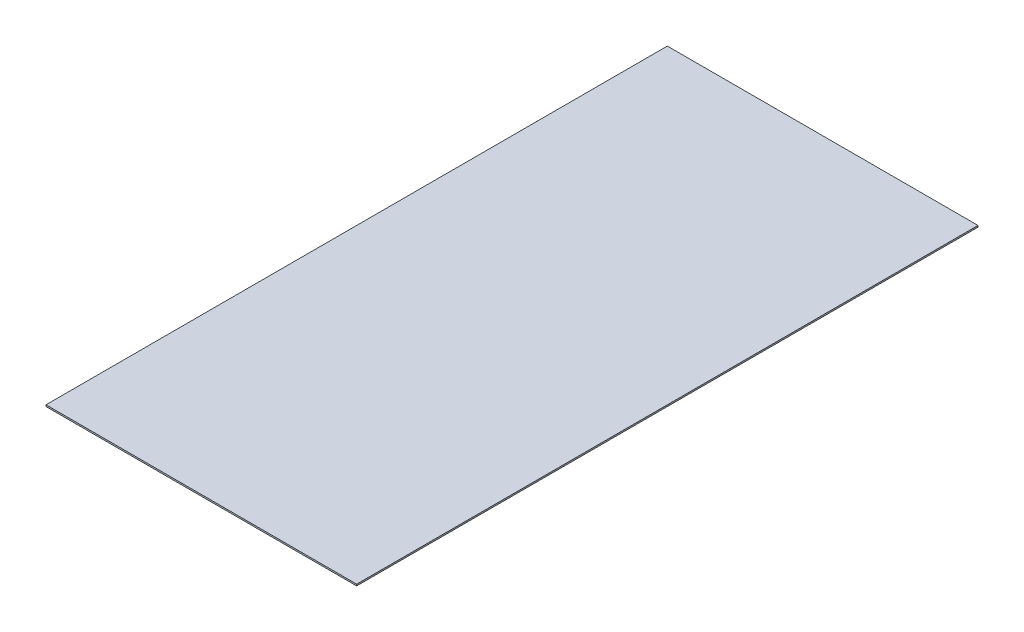
SolidWorks part; units mm, degrees
ref_plane "Front Plane" through (0, 0, 0) normal (0, 0, 1) x (1, 0, 0)
ref_plane "Top Plane" through (0, 0, 0) normal (0, 1, 0) x (1, 0, 0)
ref_plane "Right Plane" through (0, 0, 0) normal (1, 0, 0) x (0, 0, -1)
sketch "Sketch1" plane through (0, 0, 0) normal (0, 1, 0) x (1, 0, 0)
  line L1 (-254, -508) -> (254, -508)
  line L2 (-254, -508) -> (-254, 508)
  line L3 (-254, 508) -> (254, 508)
  line L4 (254, -508) -> (254, 508)
  line L5 (-254, -508) -> (254, 508) construction
  line L6 (-254, 508) -> (254, -508) construction
  point P0 (0, 0)
  dimension "D1" = 1016
  dimension "D2" = 508
extrude "Ground Plane" add sketch "Sketch1" along normal blind 2.54 contours L3 L4 L1 L2
